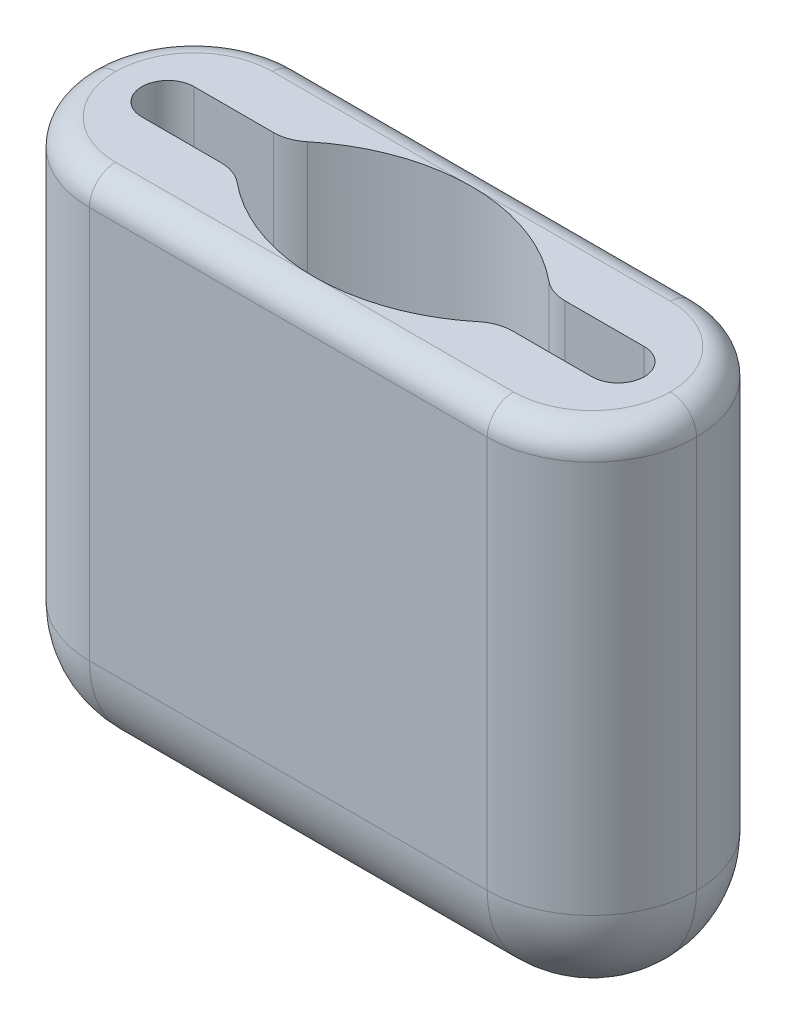
SolidWorks part; units mm, degrees
material "PET"
ref_plane "Front Plane" through (0, 0, 0) normal (0, 0, 1) x (1, 0, 0)
ref_plane "Top Plane" through (0, 0, 0) normal (0, 1, 0) x (1, 0, 0)
ref_plane "Right Plane" through (0, 0, 0) normal (1, 0, 0) x (0, 0, -1)
sketch "Sketch1" plane through (0, 0, 0) normal (0, 1, 0) x (1, 0, 0)
  line L0 (0, -1.27) -> (0, -5.3975) construction
  line L1 (-10.922, -1.27) -> (-6.35, -1.27)
  line L2 (-12.192, -1.27) -> (-12.192, 0) construction
  line L3 (-10.922, 1.27) -> (-6.35, 1.27)
  line L4 (12.192, -1.27) -> (12.192, 0) construction
  line L5 (-11.3782, -1.1852) -> (11.3782, 1.1852) construction
  line L6 (-11.3782, 1.1852) -> (11.3782, -1.1852) construction
  line L7 (0, 1.27) -> (0, 5.3975) construction
  line L8 (-12.192, 0) -> (-12.192, 1.27) construction
  line L9 (-12.192, 1.27) -> (-11.3782, 1.1852) construction
  line L10 (-12.192, 1.27) -> (-10.922, 1.27) construction
  line L11 (-12.192, -1.27) -> (-10.922, -1.27) construction
  line L12 (-12.192, -1.27) -> (-11.3782, -1.1852) construction
  line L13 (-6.35, -1.27) -> (0, -1.27) construction
  line L14 (6.35, -1.27) -> (10.922, -1.27)
  line L15 (0, 0) -> (0, -1.27) construction
  line L16 (0, -1.27) -> (6.35, -1.27) construction
  line L17 (0, 1.27) -> (6.35, 1.27) construction
  line L18 (6.35, 1.27) -> (10.922, 1.27)
  line L19 (0, 0) -> (0, 1.27) construction
  line L20 (-6.35, 1.27) -> (0, 1.27) construction
  line L21 (12.192, 0) -> (12.192, 1.27) construction
  line L22 (11.3782, 1.1852) -> (12.192, 1.27) construction
  line L23 (10.922, 1.27) -> (12.192, 1.27) construction
  line L24 (10.922, -1.27) -> (12.192, -1.27) construction
  line L25 (11.3782, -1.1852) -> (12.192, -1.27) construction
  line L27 (-14.732, -5.08) -> (14.732, -5.08)
  line L28 (-14.732, -5.08) -> (-14.732, 5.08)
  line L29 (-14.732, 5.08) -> (14.732, 5.08)
  line L30 (14.732, -5.08) -> (14.732, 5.08)
  line L31 (-14.732, -5.08) -> (14.732, 5.08) construction
  line L32 (-14.732, 5.08) -> (14.732, -5.08) construction
  arc A1 (-6.35, 1.27) -> (6.35, 1.27) centre (0, -5.3975) cw
  arc A2 (-6.35, -1.27) -> (6.35, -1.27) centre (0, 5.3975) ccw
  arc A3 (-10.922, 1.27) -> (-10.922, -1.27) centre (-10.922, 0) ccw
  arc A4 (10.922, 1.27) -> (10.922, -1.27) centre (10.922, 0) cw
  point P0 (0, 0)
  point P15 (0, 3.81)
  point P16 (0, -3.81)
  dimension "D1" = 24.384
  dimension "D2" = 2.54
  dimension "D3" = 7.62
  dimension "D4" = 12.7
  dimension "D5" = 2.54
  dimension "D6" = 1.27
extrude "Boss-Extrude1" add sketch "Sketch1" along normal blind 12.7
extrude "Boss-Extrude2" add sketch "Sketch1<2>" against normal blind 12.7 contours L27 L30 L29 L28
sketch "Sketch1<2>" plane through (0, 0, 0) normal (0, 1, 0) x (1, 0, 0) same geometry as "Sketch1"
fillet "Fillet2" radius 5.08 2 edges at (0, -12.7, -5.08) (0, -12.7, 5.08)
fillet "Fillet3" radius 5.08 8 edges at (14.732, 2.54, -5.08) (14.732, -11.2121, -3.5921) (14.732, -11.2121, 3.5921) (-14.732, 2.54, -5.08) (-14.732, -11.2121, -3.5921) (-14.732, -11.2121, 3.5921) (14.732, 2.54, 5.08) (-14.732, 2.54, 5.08)
fillet "Fillet5" radius 0.635 8 edges at (8.636, 0, 1.27) (0, 0, 3.81) (-8.636, 0, 1.27) (-12.192, 0, 0) (-8.636, 0, -1.27) (0, 0, -3.81) (8.636, 0, -1.27) (12.192, 0, 0)
fillet "Fillet6" radius 1.905 8 edges at (-6.3007, 0.2598, 1.1473) (6.3007, 0.2598, 1.1473) (6.3007, 0.2598, -1.1473) (-6.3007, 0.2598, -1.1473) (-6.35, 6.6675, 1.27) (6.35, 6.6675, 1.27) (6.35, 6.6675, -1.27) (-6.35, 6.6675, -1.27)
fillet "Fillet7" radius 1.27 6 edges at (0, 12.7, 5.08) (-13.2441, 12.7, 3.5921) (-13.2441, 12.7, -3.5921) (0, 12.7, -5.08) (13.2441, 12.7, -3.5921) (13.2441, 12.7, 3.5921)
